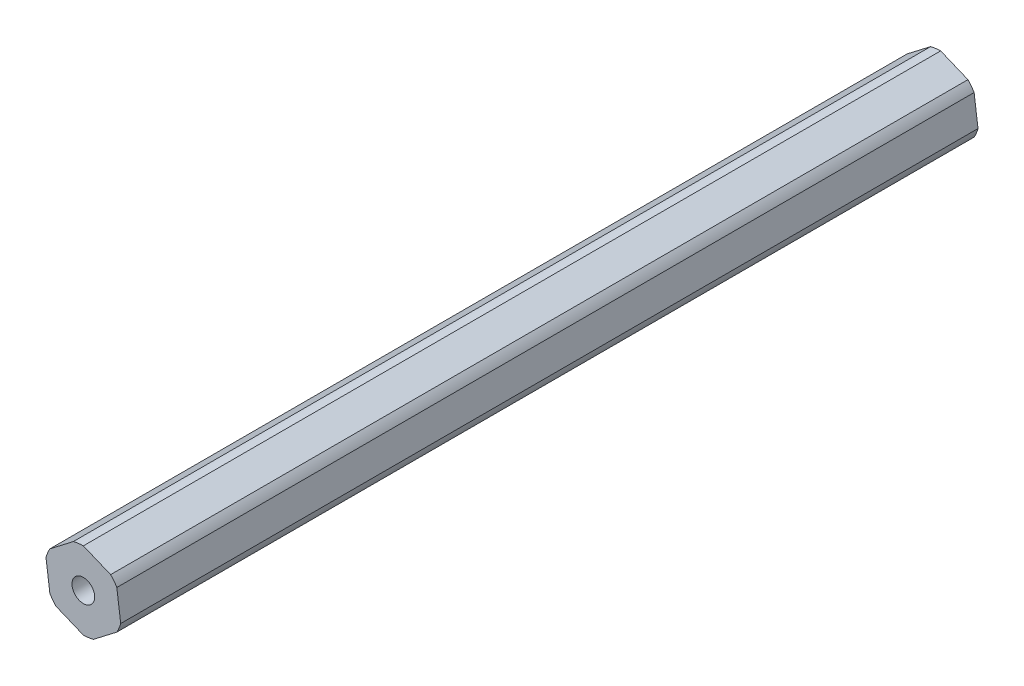
SolidWorks part; units mm, degrees
ref_plane "Front Plane" through (0, 0, 0) normal (0, 0, 1) x (1, 0, 0)
ref_plane "Top Plane" through (0, 0, 0) normal (0, 1, 0) x (1, 0, 0)
ref_plane "Right Plane" through (0, 0, 0) normal (1, 0, 0) x (0, 0, -1)
sketch "Sketch1" plane through (0, 0, 0) normal (0, 0, 1) x (1, 0, 0)
  line L1 (-1.7899, 6.6335) -> (-5.9502, 3.4354)
  line L2 (-6.6397, 1.7666) -> (-5.9502, -3.4353)
  line L3 (-4.8498, -4.8668) -> (0, -6.8707)
  line L4 (1.7899, -6.6335) -> (5.9502, -3.4354)
  line L5 (6.6397, -1.7666) -> (5.9502, 3.4353)
  line L6 (4.8498, 4.8668) -> (0, 6.8707)
  circle A0 centre (0, 0) radius 6.35 construction
  arc A1 (-5.9502, 3.4354) -> (-6.6397, 1.7666) centre (0, 0) ccw
  arc A2 (-5.9502, -3.4353) -> (-4.8498, -4.8668) centre (0, 0) ccw
  arc A3 (0, -6.8707) -> (1.7899, -6.6335) centre (0, 0) ccw
  arc A4 (5.9502, -3.4354) -> (6.6397, -1.7666) centre (0, 0) ccw
  arc A5 (5.9502, 3.4353) -> (4.8498, 4.8668) centre (0, 0) ccw
  arc A6 (0, 6.8707) -> (-1.7899, 6.6335) centre (0, 0) ccw
  dimension "D1" = 12.7
  dimension "D2" = 13.7414
extrude "Boss-Extrude1" add sketch "Sketch1" along normal blind 152.4 contours L1 A1 L2 A2 L3 A3 L4 A4 L5 A5 L6 A6
hole_wizard "#10-32 Tapped Hole2" positions "Sketch4" profile "Sketch5" tap size "#10-32" standard "ANSI Inch"
sketch "Sketch4" plane through (0, 0, 152.4) normal (0, 0, 1) x (1, 0, 0)
  point P0 (0, 0)
sketch "Sketch5" plane through (0, 0, 152.4) normal (1, 0, 0) x (0, -1, 0)
  line L0 (0, 0) -> (0, 14.8277)
  line L1 (0, 14.8277) -> (2.0193, 13.6144)
  line L2 (2.0193, 13.6144) -> (2.0193, 0)
  line L5 (2.0193, 0) -> (0, 0)
  line L10 (0, 14.8277) -> (-2.0193, 13.6144) construction
  line L11 (0, -6.35) -> (0, 107.95) construction
  dimension "Tap Drill Dia." = 4.0386
  dimension "Tap Drill Depth" = 13.6144
  dimension "Drill Angle" = 118
cosmetic thread "Hole Thread3" parameters "D1"=9.652, "D2"=4.826
